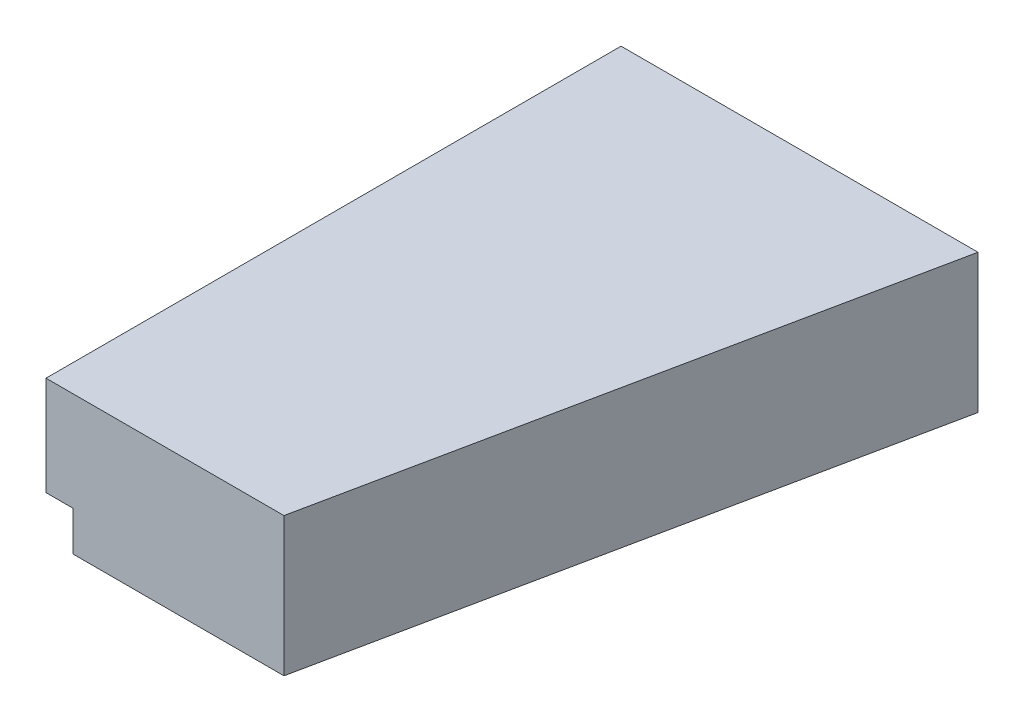
SolidWorks part; units mm, degrees
ref_plane "Front Plane" through (0, 0, 0) normal (1, 0, 0) x (0, 1, 0)
ref_plane "Top Plane" through (0, 0, 0) normal (0, 0, 1) x (0, 1, 0)
ref_plane "Right Plane" through (0, 0, 0) normal (0, 1, 0) x (-1, 0, 0)
sketch "Sketch1" plane through (0, 0, 0) normal (0, 1, 0) x (-1, 0, 0)
  line L0 (-13.4363, 2.5951) -> (16.5637, 147.5951)
  line L1 (-13.4363, -4.9049) -> (-8.4363, -4.9049)
  line L2 (-13.4363, -4.9049) -> (-13.4363, 2.5951)
  line L3 (-13.4363, 2.5951) -> (-8.4363, 2.5951)
  line L4 (-8.4363, -4.9049) -> (-8.4363, 2.5951)
  line L13 (-13.4363, 2.5951) -> (16.5637, 147.5951)
  line L14 (-13.4363, 2.5951) -> (-3.6437, 0.569)
  line L15 (-13.4363, 2.5951) -> (66.5637, 2.5951) construction
  line L16 (-13.4363, 2.5951) -> (-13.4363, 137.5951) construction
  line L17 (-13.4363, 137.5951) -> (66.5637, 137.5951) construction
  line L18 (66.5637, 2.5951) -> (66.5637, 137.5951) construction
  line L19 (66.5637, 137.5951) -> (16.5637, 137.5951)
  line L20 (66.5637, 137.5951) -> (66.5637, 147.5951)
  line L21 (66.5637, 147.5951) -> (16.5637, 147.5951)
  line L22 (16.5637, 137.5951) -> (16.5637, 147.5951)
  line L23 (16.5637, 147.5951) -> (26.3563, 145.569)
  line L24 (-3.6437, 0.569) -> (26.3563, 145.569)
  line L25 (-8.4363, 2.5951) -> (-3.2246, 2.5951)
  line L27 (-3.2246, 2.5951) -> (66.5637, 2.5951)
  line L28 (-3.2246, 2.5951) -> (-3.2246, 7.5951)
  line L29 (-3.2246, 7.5951) -> (66.5637, 7.5951)
  line L30 (66.5637, 2.5951) -> (66.5637, 7.5951)
  line L35 (66.5637, 147.5951) -> (76.5637, 147.5951)
  line L36 (66.5637, 147.5951) -> (66.5637, 2.5951)
  line L37 (66.5637, 2.5951) -> (76.5637, 2.5951)
  line L38 (76.5637, 147.5951) -> (76.5637, 2.5951)
  dimension "D1" = 7.5
  dimension "D2" = 5
  dimension "D3" = 135
  dimension "D4" = 80
  dimension "D5" = 10
  dimension "D7" = 10
  dimension "D9" = 5
  dimension "D8" = 10
  dimension "D6" = 50
extrude "Boss-Extrude1" add sketch "Sketch1" along normal blind 35 contours L24 L19 L20 L21 L23 | L19 L24 L23 L22 | L3 L25 L24 L19 L22 L0 | L29 L28 L24 | L27 L30 L29 L24 | L38 L35 L20 L36 L30 L37 region at (-5.7274, 0, 70.7433) region at (-20.91, 0, 142.2574) region at (-45.5816, 0, 142.6608) region at (-71.5637, 0, 75.0951) region at (2.8797, 0, 5.9284) region at (-31.9275, 0, 5.0889)
sketch "Sketch2" plane through (0, 35, 0) normal (0, 1, 0) x (-1, 0, 0)
  line L0 (16.5637, 147.5951) -> (76.5637, 147.5951)
  line L1 (76.5637, 147.5951) -> (76.5637, 2.5951)
  line L2 (76.5637, 2.5951) -> (-13.4363, 2.5951)
  line L3 (-13.4363, 2.5951) -> (16.5637, 147.5951)
  line L5 (-13.4363, 2.5951) -> (76.5637, 2.5951) construction
extrude "Boss-Extrude2" add sketch "Sketch2" against normal blind 10
sketch "Sketch3" plane through (0, 0, 0) normal (0, -1, 0) x (1, 0, 0)
  line L1 (-24.7065, 147.5951) -> (-66.5637, 147.5951)
  line L2 (-24.7065, 147.5951) -> (-24.7065, 137.5951)
  line L3 (-24.7065, 137.5951) -> (-66.5637, 137.5951)
  line L4 (-66.5637, 147.5951) -> (-66.5637, 137.5951)
  line L17 (-76.5637, 147.5951) -> (-16.5637, 147.5951) construction
  line L22 (2.1901, 7.5951) -> (-24.7065, 137.5951)
  line L23 (2.1901, 7.5951) -> (11.9827, 9.6211)
  line L24 (-24.7065, 137.5951) -> (-14.9139, 139.6211)
  line L26 (11.9827, 9.6211) -> (-14.9139, 139.6211)
  line L27 (13.4363, 2.5951) -> (-16.5637, 147.5951) construction
  line L28 (-27.9565, 140.8451) -> (-63.3137, 140.8451)
  line L29 (-63.3137, 144.3451) -> (-63.3137, 140.8451)
  line L30 (-27.9565, 144.3451) -> (-63.3137, 144.3451)
  line L31 (-27.9565, 144.3451) -> (-27.9565, 140.8451)
  line L32 (-20.8654, 135.071) -> (-17.438, 135.7801)
  line L33 (8.1416, 12.1453) -> (-17.438, 135.7801)
  line L34 (4.7142, 11.4361) -> (8.1416, 12.1453)
  line L35 (4.7142, 11.4361) -> (-20.8654, 135.071)
  line L36 (-17.438, 135.7801) -> (-20.8654, 135.071)
  line L37 (-20.8654, 135.071) -> (-23.4566, 147.5951)
  line L38 (-17.438, 135.7801) -> (-19.8825, 147.5951)
  line L39 (-27.9565, 140.8451) -> (-18.4859, 140.8451)
  line L40 (-27.9565, 144.3451) -> (-19.2101, 144.3451)
  line L41 (-19.2101, 144.3451) -> (-18.4859, 140.8451)
  dimension "D1" = 3.25
extrude "Cut-Extrude1" cut sketch "Sketch3" against normal blind 10 contours L31 L30 L29 L28 | L35 L34 L33 L32 region at (-45.6351, 0, 142.5951) region at (-6.3619, 0, 73.6081)
sketch "Sketch4" plane through (0, 0, 22.5951) normal (0, 1, 0) x (1, 0, 0)
  line L5 (13.4363, 20) -> (-76.5637, 20) construction
  line L6 (-66.5637, 15) -> (2.1901, 15)
  line L7 (-66.5637, 15) -> (-66.5637, 20)
  line L8 (-66.5637, 20) -> (2.1901, 20)
  line L9 (2.1901, 15) -> (2.1901, 20)
  line L10 (2.1901, 15) -> (3.2246, 20)
  line L11 (2.1901, 15) -> (-24.7065, -115) construction
  line L12 (3.2246, 20) -> (2.1901, 20)
  line M13 (2.1901, 15) -> (-66.5637, 15)
  line M20 (-76.5637, 20) -> (13.4363, 20)
extrude "Cut-Extrude2" cut sketch "Sketch4" along normal blind 0.625 contours L9 L7 M13 M20 | L10 L9 M20 region at (-32.1868, 0, 5.0951) region at (2.5349, 0, 4.2617)
sketch "Sketch5" plane through (0, 0, 7.5951) normal (0, 0, 1) x (1, 0, 0)
  line L1 (-66.5637, 0.625) -> (-59.3137, 0.625) construction
  line L2 (-66.5637, 0.625) -> (-66.5637, 5.625) construction
  line L3 (-66.5637, 5.625) -> (-59.3137, 5.625) construction
  line L4 (-59.3137, 0.625) -> (-59.3137, 5.625) construction
  circle A0 centre (-59.3137, 5.625) radius 1.9
  dimension "D3" = 3.8
  dimension "D1" = 5
  dimension "D2" = 7.25
extrude "Cut-Extrude3" cut sketch "Sketch5" against normal up to next contours A0
sketch "Sketch6" plane through (0, 0, 7.5951) normal (0, 0, 1) x (1, 0, 0)
  circle A0 centre (-59.3137, 5.625) radius 3.35
  dimension "D1" = 6.7
extrude "Cut-Extrude4" cut sketch "Sketch6" against normal blind 2.5
pattern_linear "LPattern1" count 2 spacing 52.5 along (1, 0, 0) of "Cut-Extrude4", "Cut-Extrude3"
sketch "Sketch7" plane through (0, 0, 0) normal (0, -1, 0) x (1, 0, 0)
  line L0 (-66.5637, 2.5951) -> (-76.5637, 2.5951) construction
  line L1 (-76.5637, 147.5951) -> (-73.3137, 147.5951)
  line L2 (-76.5637, 147.5951) -> (-76.5637, 2.5951)
  line L3 (-76.5637, 2.5951) -> (-73.3137, 2.5951)
  line L4 (-73.3137, 147.5951) -> (-73.3137, 2.5951) construction
  line L5 (-76.5637, 147.5951) -> (-16.5637, 147.5951) construction
  line L6 (-66.5637, 2.5951) -> (-69.8137, 2.5951)
  line L7 (-66.5637, 2.5951) -> (-66.5637, 147.5951)
  line L8 (-66.5637, 147.5951) -> (-69.8137, 147.5951)
  line L9 (-69.8137, 2.5951) -> (-69.8137, 147.5951) construction
  line L11 (-69.8137, 2.5951) -> (-73.3137, 2.5951)
  line L12 (-69.8137, 2.5951) -> (-69.8137, 147.5951)
  line L13 (-69.8137, 147.5951) -> (-73.3137, 147.5951)
  line L14 (-73.3137, 2.5951) -> (-73.3137, 147.5951)
  line M13 (-76.5637, 2.5951) -> (-66.5637, 2.5951)
  line M20 (-16.5637, 147.5951) -> (-76.5637, 147.5951)
  line M21 (-76.5637, 147.5951) -> (-76.5637, 2.5951)
  dimension "D1" = 3.25
  dimension "D2" = 3.25
extrude "Cut-Extrude5" cut sketch "Sketch7" against normal blind 10 contours L14 L12 M13 M20 | L14 M13 M20 M21 region at (-74.9387, 0, 75.0951) region at (-71.5637, 0, 75.0951)
equation "\"whitekey_cutout_length\"= 101.5"
equation "\"key_mount_recess_length\"=50"
equation "\"key_mount_recess_height\"=12.5"
equation "\"key_mount_recess_depth\"=1.5"
equation "\"wall_thickness\"=10"
equation "\"guide_brace_height\"=20"
equation "\"guide_brace_thickness\"=2"
equation "\"dowel_recess_depth\"=10"
equation "\"dowel_recess_offset\"=3.25"
equation "\"dowel_insert_tolerance\"=0.1"
equation "\"base_mount_height\"=40"
equation "\"base_rear_length\"=80"
equation "\"base_front_length\"=111.5"
equation "\"screw_hole_wall_offset\"=7.25"
equation "\"screw_hole_edge_inset\"=\"dowel_recess_depth\"/2"
equation "\"screw_hole_diameter\"=3.8"
equation "\"screw_head_hole_diameter\"=6.7"
equation "\"screw_nut_hole_side_len\"=3.5"
equation "\"screw_nut_recess_offset\"=0.35"
equation "\"screw_head_and_nut_recess_depth\"=2.5"
equation "\"screw_shaft_diameter\"=3.5"
equation "\"switch_board_width\"=30"
equation "\"switch_board_thickness\"=1.6"
equation "\"switch_board_wall_offset\"=11.5"
equation "\"heatset_insert_hole_diameter\"=4.8"
equation "\"heatset_insert_hole_depth\"=3.8"
equation "\"front_rear_panel_width\"=23.75"
equation "\"front_panel_height\"=24"
equation "\"front_rear_panel_recess_depth\"=5"
equation "\"rod_diameter\"=5"
equation "\"rod_head_diameter\"=8"
equation "\"rod_length_adj\"=0.5"
equation "\"rod_insert_length\"=2.8"
equation "\"switch_black_key_mount_height\"=8"
equation "\"switch_white_key_mount_height\"=3"
equation "\"D5@Sketch1\"=\"wall_thickness\""
equation "\"D7@Sketch1\"=\"wall_thickness\""
equation "\"D2@Sketch1\"=\"wall_thickness\"/2"
equation "\"D4@Sketch1\"=\"base_rear_length\""
equation "\"D3@Sketch1\"=\"interface_panel_height\""
equation "\"D1@Sketch1\"=\"wall_thickness\"*0.75"
equation "\"whitekey_spacing\"=1.25"
equation "\"D1@Boss-Extrude1\"=\"side_panel_depth\""
equation "\"D9@Sketch1\"=\"wall_thickness\"/2"
equation "\"D1@Boss-Extrude2\"=\"wall_thickness\""
equation "\"D8@Sketch1\"=\"wall_thickness\""
equation "\"D1@Sketch3\"=\"dowel_recess_offset\""
equation "\"D1@Cut-Extrude1\"=\"dowel_recess_depth\""
equation "\"side_panel_depth\"=35"
equation "\"D1@Sketch5\"=\"screw_hole_edge_inset\""
equation "\"D2@Sketch5\"=\"screw_hole_wall_offset\""
equation "\"D3@Sketch5\"=\"screw_hole_diameter\""
equation "\"D1@Sketch6\"=\"screw_head_hole_diameter\""
equation "\"D1@Cut-Extrude4\"=\"screw_head_and_nut_recess_depth\""
equation "\"D3@LPattern1\"=\"base_rear_length\"-\"screw_hole_wall_offset\"*2-\"wall_thickness\"-3"
equation "\"D1@Sketch7\"=\"dowel_recess_offset\""
equation "\"D2@Sketch7\"=\"dowel_recess_offset\""
equation "\"D1@Cut-Extrude5\"=\"front_rear_panel_recess_depth\"*2"
equation "\"D1@Cut-Extrude2\"=\"whitekey_spacing\"/2"
equation "\"interface_panel_height\"=135"
equation "\"interface_panel_roof_length\"=50"
equation "\"D6@Sketch1\"=\"interface_panel_roof_length\""
